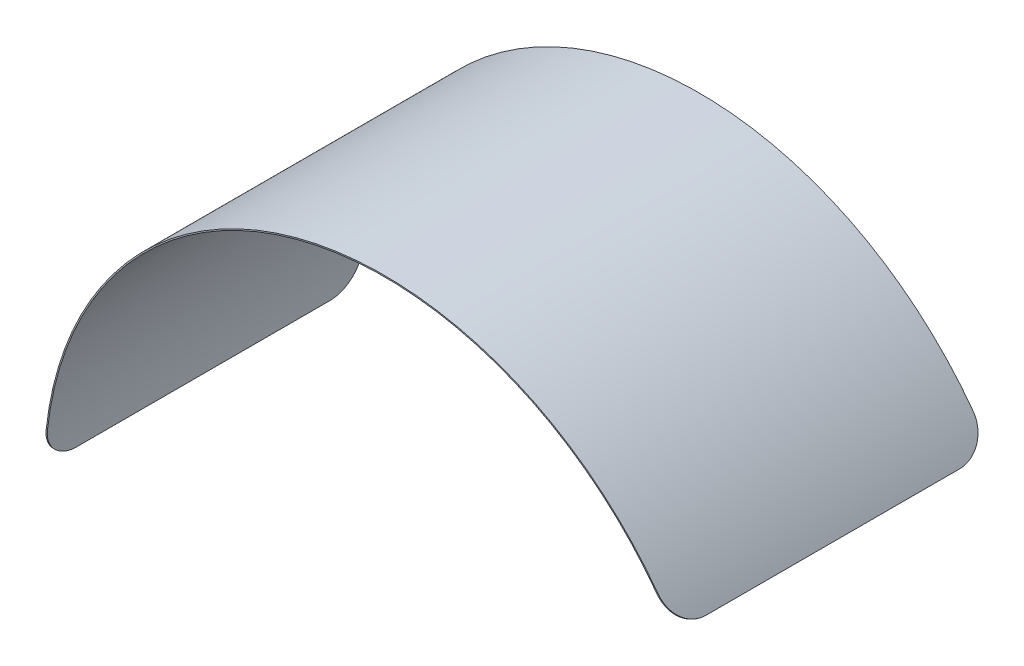
SolidWorks part; units mm, degrees
ref_plane "Front Plane" through (0, 0, 0) normal (0, 0, 1) x (1, 0, 0)
ref_plane "Top Plane" through (0, 0, 0) normal (0, 1, 0) x (1, 0, 0)
ref_plane "Right Plane" through (0, 0, 0) normal (1, 0, 0) x (0, 0, -1)
sketch "Sketch1" plane through (0, 0, 0) normal (0, 0, 1) x (1, 0, 0)
  line L0 (2047.0299, 548.5) -> (2043.5658, 546.5) construction
  line L1 (0, 0) -> (4, 0) construction
  line L2 (2036.8724, 565.7286) -> (2033.4453, 563.6658)
  line L3 (0.1823, 19.9992) -> (4.1817, 19.9262)
  arc A0 (0, 0) -> (2047.0299, 548.5) centre (1097, 0) cw construction
  arc A1 (4, 0) -> (2043.5658, 546.5) centre (1097, 0) cw construction
  arc A2 (0.1823, 19.9992) -> (2036.8724, 565.7286) centre (1097, 0) cw
  arc A3 (4.1817, 19.9262) -> (2033.4453, 563.6658) centre (1097, 0) cw
  dimension "D1" = 1097
  dimension "D3" = 150
  dimension "D5" = 20
  dimension "D6" = 20
  dimension "D2" = 4
  dimension "D4" = 4
extrude "Boss-Extrude1" add sketch "Sketch1" along normal blind 1018.2
fillet "Fillet1" radius 100 4 edges at (2.182, 19.9627, 1018.2) (2.182, 19.9627, 0) (2035.1589, 564.6972, 0) (2035.1589, 564.6972, 1018.2)
